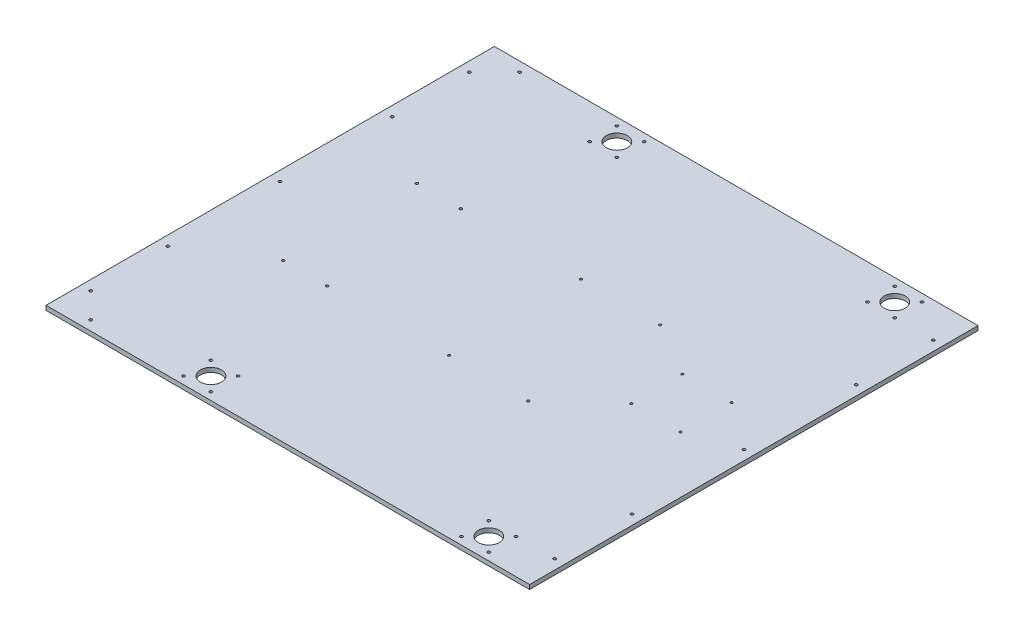
SolidWorks part; units mm, degrees
ref_plane "Front Plane" through (0, 0, 0) normal (0, 0, 1) x (1, 0, 0)
ref_plane "Top Plane" through (0, 0, 0) normal (0, 1, 0) x (1, 0, 0)
ref_plane "Right Plane" through (0, 0, 0) normal (1, 0, 0) x (0, 0, -1)
sketch "Sketch1" plane through (0, 0, 0) normal (1, 0, 0) x (0, 0, -1)
  line L0 (0, 0) -> (-510, 0)
  line L1 (-510, 0) -> (-510, 5)
  line L2 (-510, 5) -> (0, 5)
  line L6 (0, 5) -> (0, 0)
  dimension "D1" = 510
  dimension "D2" = 5
extrude "Boss-Extrude1" add sketch "Sketch1" along normal blind 550
sketch "BotthomHoles-Sketch2" plane through (0, 5, 0) normal (0, 1, 0) x (1, 0, 0)
  line L0 (550, -3.175) -> (0, -3.175) construction
  line L2 (550, 0) -> (550, -510) construction
  line L3 (550, 0) -> (0, 0) construction
  line L4 (550, -510) -> (0, -510) construction
  line L7 (0, 0) -> (0, -510) construction
  line L8 (550, 0) -> (550, -510) construction
  circle A0 centre (479.425, -24.175) radius 12
  circle A2 centre (463.925, -8.675) radius 1.5875
  circle A3 centre (494.925, -8.675) radius 1.5875
  circle A6 centre (463.925, -39.675) radius 1.5875
  circle A7 centre (494.925, -39.675) radius 1.5875
  circle A8 centre (39.6875, -11.1125) radius 1.5875
  circle A10 centre (178.925, -39.675) radius 1.5875
  circle A11 centre (147.925, -39.675) radius 1.5875
  circle A12 centre (178.925, -8.675) radius 1.5875
  circle A13 centre (147.925, -8.675) radius 1.5875
  circle A14 centre (163.425, -24.175) radius 12
  circle A15 centre (39.6875, -498.8875) radius 1.5875
  circle A16 centre (147.925, -501.325) radius 1.5875
  circle A17 centre (178.925, -501.325) radius 1.5875
  circle A18 centre (147.925, -470.325) radius 1.5875
  circle A19 centre (178.925, -470.325) radius 1.5875
  circle A20 centre (463.925, -470.325) radius 1.5875
  circle A21 centre (463.925, -501.325) radius 1.5875
  circle A22 centre (494.925, -470.325) radius 1.5875
  circle A23 centre (494.925, -501.325) radius 1.5875
  circle A25 centre (163.425, -485.825) radius 12
  circle A26 centre (479.425, -485.825) radius 12
  circle A27 centre (11.1125, -39.6875) radius 1.5875
  circle A28 centre (11.1125, -127.5) radius 1.5875
  circle A29 centre (11.1125, -255) radius 1.5875
  circle A30 centre (11.1125, -382.5) radius 1.5875
  circle A31 centre (11.1125, -470.3125) radius 1.5875
  circle A32 centre (538.8875, -470.3125) radius 1.5875
  circle A33 centre (538.8875, -382.5) radius 1.5875
  circle A34 centre (538.8875, -255) radius 1.5875
  circle A35 centre (538.8875, -127.5) radius 1.5875
  circle A36 centre (538.8875, -39.6875) radius 1.5875
  point P11 (0, 0)
  dimension "D9" = 3.175
  dimension "D10" = 24
  dimension "D13" = 3.175
  dimension "D29" = 3.175
  dimension "D2" = 8.675
  dimension "D5" = 15.5
  dimension "D6" = 31
  dimension "D7" = 15.5
  dimension "D8" = 31
  dimension "D11" = 21
  dimension "D12" = 39.6875
  dimension "D15" = 31
  dimension "D16" = 15.5
  dimension "D17" = 316
  dimension "D3" = 70.575
  dimension "D4" = 11.1125
  dimension "D18" = 8.675
  dimension "D19" = 15.5
  dimension "D20" = 31
  dimension "D21" = 11.1125
  dimension "D22" = 39.6875
  dimension "D23" = 39.6875
  dimension "D24" = 127.5
  dimension "D25" = 127.5
  dimension "D26" = 127.5
  dimension "D27" = 11.1125
  dimension "D28" = 11.1125
extrude "BottomHoles-Cut-Extrude1" cut sketch "BotthomHoles-Sketch2" against normal through all
sketch "BottomPSUHolesSketch2" plane through (0, 5, 0) normal (0, 1, 0) x (1, 0, 0)
  line L0 (0, 0) -> (0, -510) construction
  line L1 (550, 0) -> (0, 0) construction
  line L2 (550, -510) -> (0, -510) construction
  circle A0 centre (90.8, -179) radius 1.5
  circle A1 centre (140.8, -179) radius 1.5
  circle A2 centre (90.8, -331) radius 1.5
  circle A3 centre (140.8, -331) radius 1.5
  dimension "D6" = 3
  dimension "D1" = 152
  dimension "D2" = 50
  dimension "D3" = 90.8
  dimension "D4" = 179
  dimension "D5" = 179
extrude "BottomPSUHolesCut-Extrude1" cut sketch "BottomPSUHolesSketch2" against normal through all
sketch "BottomMainboardHolesSketch2" plane through (0, 5, 0) normal (0, 1, 0) x (1, 0, 0)
  line L0 (550, 0) -> (0, 0) construction
  line L1 (0, 0) -> (0, -510) construction
  line L2 (550, 0) -> (550, -510) construction
  circle A0 centre (278.5, -180) radius 1.35
  circle A1 centre (368.5, -180) radius 1.35
  circle A2 centre (278.5, -330) radius 1.35
  circle A3 centre (368.5, -330) radius 1.35
  circle A4 centre (429.7, -216) radius 1.35
  circle A5 centre (485.7, -216) radius 1.35
  circle A6 centre (429.7, -274) radius 1.35
  circle A7 centre (485.7, -274) radius 1.35
  dimension "D6" = 2.7
  dimension "D7" = 2.7
  dimension "D1" = 90
  dimension "D2" = 150
  dimension "D3" = 180
  dimension "D4" = 58
  dimension "D5" = 56
  dimension "D8" = 216
  dimension "D9" = 278.5
  dimension "D10" = 64.3
extrude "BottomMainboardHolesCut-Extrude1" cut sketch "BottomMainboardHolesSketch2" against normal through all
equation "\"LowerRailWidth\"= 2.00in"
equation "\"RailThickness\"= .125in'Spec"
equation "\"StepperHoleDiameter\"= 24mm"
equation "\"StepperMountingHoleDiameter\"= 3.175mm"
equation "\"SideRailLength\"= 550mm"
equation "\"StepperMountingHoleDistance\"= 31mm'Spec"
equation "\"StepperMountingHoleOffsetFromLeftOrRightSide\"= \"StepperMountingHoleOffsetFromItsSide\" + \"RailThickness\""
equation "\"HoleOffsetFromEdge\"= \"RailThickness\" * 2.5"
equation "\"HoleOffsetFromSide\"= \"RailThickness\" * 3.5"
equation "\"StepperMountingHoleOffsetFromItsSide\"= 5.5mm'Spec"
equation "\"FasteningHoleDiameter\"= .125in"
equation "\"D2@BotthomHoles-Sketch2\" = \"StepperMountingHoleOffsetFromLeftOrRightSide\""
equation "\"D5@BotthomHoles-Sketch2\" = \"StepperMountingHoleDistance\" / 2"
equation "\"D6@BotthomHoles-Sketch2\" = \"StepperMountingHoleDistance\""
equation "\"D7@BotthomHoles-Sketch2\" = \"StepperMountingHoleDistance\" / 2"
equation "\"D8@BotthomHoles-Sketch2\" = \"StepperMountingHoleDistance\""
equation "\"D9@BotthomHoles-Sketch2\" = \"StepperMountingHoleDiameter\""
equation "\"D10@BotthomHoles-Sketch2\" = \"StepperHoleDiameter\""
equation "\"D1@Boss-Extrude1\"=\"SideRailLength\""
equation "\"BedOverlap\"= 20mm"
equation "\"BedThirdSize\"= 70mm"
equation "\"BedInnerSquareWidth\"= \"BedThirdSize\" * 3'Equals 210"
equation "\"BedInnerSquareLength\"= \"BedInnerSquareWidth\""
equation "\"BedLWidth\"= \"BedThirdSize\" + \"BedOverlap\"'Equals 90"
equation "\"BedLength\"= \"BedInnerSquareLength\" + \"BedLWidth\" * 2 - \"BedOverlap\" * 2 + \"BedIncreasedByLength\"'Equals 350"
equation "\"DistanceBetweenFrontToBackStepperHoles\"= \"BedLength\" - \"DistanceFromBedFrontToFirstLeftStepperHole\"'Equals 316"
equation "\"DistanceFromBedFrontToFirstLeftStepperHole\"= \"LeadScrewNutPadSize\" + 10mm'Equals 34"
equation "\"DistanceFromFrontSideToBedFront\"= \"RailThickness\" + \"BeltTensionerDepth\" + 10mm'Equals 36.575"
equation "\"20TGT2PulleyDiameter\"= 17.9mm'Spec"
equation "\"BeltTensionerBackWallThickness\"= 4mm"
equation "\"BeltTensionerSpaceBetweenPulleyAndWall\"= 1.5mm"
equation "\"BeltTensionerInnerDepth\"= \"20TGT2PulleyDiameter\" + \"BeltTensionerSpaceBetweenPulleyAndWall\""
equation "\"BeltTensionerDepth\"= \"BeltTensionerBackWallThickness\" + \"BeltTensionerInnerDepth\"'Equals 23.4"
equation "\"BedIncreasedByLength\"= 0mm"
equation "\"LowerCornerBlockWidth\"= \"LowerRailWidth\" - \"RailThickness\" * 2'Room for left front stepper"
equation "\"D12@BotthomHoles-Sketch2\"=\"CornerEnclosureOffset\""
equation "\"D13@BotthomHoles-Sketch2\"=\"FasteningHoleDiameter\""
equation "\"CornerEnclosureOffset\"= \"LowerCornerBlockWidth\" - \"HoleOffsetFromEdge\" + \"RailThickness\""
equation "\"LowerCornerBlockY1FromSide\"= \"HoleOffsetFromSide\""
equation "\"D15@BotthomHoles-Sketch2\"=\"StepperMountingHoleDistance\""
equation "\"D16@BotthomHoles-Sketch2\"=\"StepperMountingHoleDistance\"/2"
equation "\"D17@BotthomHoles-Sketch2\"=\"DistanceBetweenFrontToBackStepperHoles\""
equation "\"DistanceFromFrontSideToFirstLeftStepperHole\"= \"DistanceFromFrontSideToBedFront\" + \"DistanceFromBedFrontToFirstLeftStepperHole\"'Equals 70.575"
equation "\"LeadScrewNutMountingHoleFlangeDiameter\"= 22mm'Spec"
equation "\"LeadScrewNutPadSize\"= \"LeadScrewNutMountingHoleFlangeDiameter\" + 2mm'Equals 24"
equation "\"D3@BotthomHoles-Sketch2\"=\"DistanceFromFrontSideToFirstLeftStepperHole\""
equation "\"LowerEnclosureThickness\"= 5mm"
equation "\"FrontBackRailLength\"= 510mm"
equation "\"D4@BotthomHoles-Sketch2\"=\"LowerCornerBlockY1FromSide\""
equation "\"D1@Sketch1\"=\"FrontBackRailLength\""
equation "\"D18@BotthomHoles-Sketch2\"=\"StepperMountingHoleOffsetFromLeftOrRightSide\""
equation "\"D19@BotthomHoles-Sketch2\"=\"StepperMountingHoleDistance\"/2"
equation "\"D20@BotthomHoles-Sketch2\"=\"StepperMountingHoleDistance\""
equation "\"D21@BotthomHoles-Sketch2\"=\"LowerCornerBlockY1FromSide\""
equation "\"D22@BotthomHoles-Sketch2\"=\"CornerEnclosureOffset\""
equation "\"D23@BotthomHoles-Sketch2\"=\"CornerEnclosureOffset\""
equation "\"FrontOrBackEnclosureOffsets\"= \"FrontBackRailLength\" / 4"
equation "\"D24@BotthomHoles-Sketch2\"=\"FrontOrBackEnclosureOffsets\""
equation "\"D25@BotthomHoles-Sketch2\"=\"FrontOrBackEnclosureOffsets\""
equation "\"D26@BotthomHoles-Sketch2\"=\"FrontOrBackEnclosureOffsets\""
equation "\"D27@BotthomHoles-Sketch2\"=\"LowerCornerBlockY1FromSide\""
equation "\"D28@BotthomHoles-Sketch2\"=\"LowerCornerBlockY1FromSide\""
equation "\"D29@BotthomHoles-Sketch2\"=\"FasteningHoleDiameter\""
equation "\"D2@Sketch1\"=\"LowerEnclosureThickness\""
equation "\"24VPSUMountingHolesShortDistanceBetween\"= 50mm'Yours may differ"
equation "\"24VPSUMountingHolesLongDistanceBetween\"= 152mm'Yours may differ"
equation "\"24VPSUMountingHoleOffsetFromEitherSide\"= 30mm'Yours may differ"
equation "\"24VPSUMountingHoleOffsetFromEdge\"= \"24VPSUMountingHoleOffsetFromEitherSide\" + \"LowerRailWidth\" + 10mm'Yours may differ"
equation "\"24VPSUMountingHoleDiameter\"= 3mm'Yours may differ"
equation "\"D2@BottomPSUHolesSketch2\" = \"24VPSUMountingHolesShortDistanceBetween\""
equation "\"D1@BottomPSUHolesSketch2\" = \"24VPSUMountingHolesLongDistanceBetween\""
equation "\"D3@BottomPSUHolesSketch2\" = \"24VPSUMountingHoleOffsetFromEdge\""
equation "\"D4@BottomPSUHolesSketch2\" =  ( \"FrontBackRailLength\" - \"24VPSUMountingHolesLongDistanceBetween\" )  / 2"
equation "\"D6@BottomPSUHolesSketch2\" = \"24VPSUMountingHoleDiameter\""
equation "\"RPi4BoardLength\"= 85mm'Spec"
equation "\"RPi4BoardWidth\"= 56mm'Spec"
equation "\"RPi4BoardMountingHoleOffsetFromEdge\"= 3.5mm'Spec"
equation "\"RPi4BoardMountingHoleDiameter\"= 2.7mm'Spec"
equation "\"OctopusV1.1BoardLength\"= 160mm'Spec"
equation "\"OctopusV1.1BoardWidth\"= 100mm'Spec"
equation "\"OctopusV1.1BoardMountingHoleOffsetFromAllEdges\"= 3.5mm'Spec"
equation "\"OctopusV1.1BoardMountingHoleLengthDistanceBetween\"= 150mm'Spec"
equation "\"OctopusV1.1BoardMountingHoleWidthDistanceBetween\"= 90mm'Spec"
equation "\"D2@BottomMainboardHolesSketch2\" = \"OctopusV1.1BoardMountingHoleLengthDistanceBetween\""
equation "\"D3@BottomMainboardHolesSketch2\" =  ( \"FrontBackRailLength\" - \"OctopusV1.1BoardMountingHoleLengthDistanceBetween\" )  / 2"
equation "\"D4@BottomMainboardHolesSketch2\" = \"RPi4BoardMountingHoleLengthDistanceBetween\""
equation "\"D5@BottomMainboardHolesSketch2\" = \"RPi4BoardWidth\""
equation "\"D6@BottomMainboardHolesSketch2\" = \"OctopusV1.1BoardMountingHoleDiameter\""
equation "\"D7@BottomMainboardHolesSketch2\" = \"RPi4BoardMountingHoleDiameter\""
equation "\"RPi4BoardMountingHoleLengthDistanceBetween\"= 58mm'Spec"
equation "\"OctopusV1.1BoardMountingHoleDiameter\"= 2.7mm'Spec"
equation "\"D1@BottomMainboardHolesSketch2\" = \"OctopusV1.1BoardMountingHoleWidthDistanceBetween\""
equation "\"D8@BottomMainboardHolesSketch2\" =  ( \"FrontBackRailLength\" - \"RPi4BoardLength\" )  / 2 + \"RPi4BoardMountingHoleOffsetFromEdge\""
equation "\"D9@BottomMainboardHolesSketch2\" = \"SideRailLength\" / 2 + \"OctopusV1.1BoardMountingHoleOffsetFromAllEdges\""
equation "\"D10@BottomMainboardHolesSketch2\" = \"LowerRailWidth\" + \"RPi4BoardMountingHoleOffsetFromEdge\" + 10mm"
